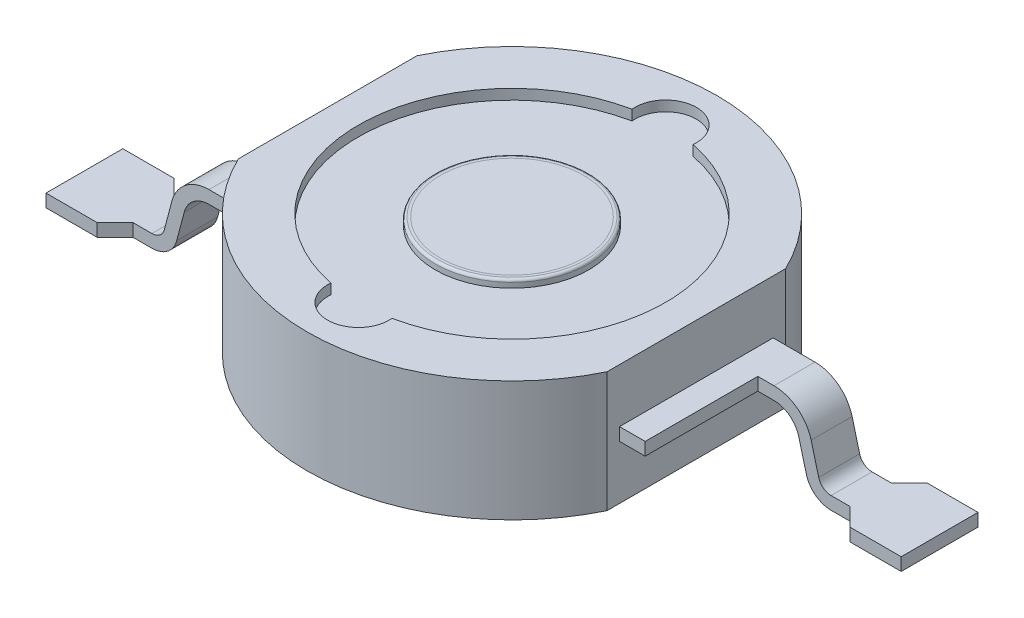
SolidWorks part; units mm, degrees
ref_plane "Front Plane" through (0, 0, 0) normal (0, 0, 1) x (1, 0, 0)
ref_plane "Top Plane" through (0, 0, 0) normal (0, 1, 0) x (1, 0, 0)
ref_plane "Right Plane" through (0, 0, 0) normal (1, 0, 0) x (0, 0, -1)
sketch "Sketch1" plane through (0, 0, 0) normal (0, 1, 0) x (1, 0, 0)
  circle A0 centre (0, 0) radius 4
  dimension "D1" = 8
extrude "Extrude1" add sketch "Sketch1" along normal blind 2.6
sketch "Sketch2" plane through (0, 2.6, 0) normal (0, 1, 0) x (1, 0, 0)
  line L0 (0, 4) -> (0, -4) construction
  line L1 (-3.6, 4) -> (3.6, 4)
  line L2 (-3.6, 4) -> (-3.6, -4)
  line L3 (-3.6, -4) -> (3.6, -4)
  line L4 (3.6, 4) -> (3.6, -4)
  circle A0 centre (0, 0) radius 4 construction
  arc A1 (-0.597, 2.94) -> (-0.597, -2.94) centre (0, 0) ccw
  arc A2 (-0.597, -2.94) -> (0.597, -2.94) centre (0, -3) ccw
  arc A3 (0.597, 2.94) -> (-0.597, 2.94) centre (0, 3) ccw
  arc A4 (0.597, -2.94) -> (0.597, 2.94) centre (0, 0) ccw
  arc A5 (-0.597, 2.94) -> (0.597, 2.94) centre (0, 0) cw construction
  arc A6 (0.597, -2.94) -> (-0.597, -2.94) centre (0, 0) cw construction
  point P4 (0, 4)
  circle M1 centre (0, 0) radius 4
  dimension "D2" = 6
  dimension "D4" = 0.6
  dimension "D1" = 7.2
extrude "Extrude2" cut sketch "Sketch2" against normal up to next (2.6 mm away) flip side to cut contours A2 A4 A3 A1 | L4 L2 A4 A2 A1 A3 M1 region at (2.0672, 2.6, -3.2981) region at (0, 2.6, 0)
extrude "Cut-Extrude1" cut sketch "Sketch2<3>" against normal blind 0.2 contours A2 A4 A3 A1 region at (0, 2.6, 0)
sketch "Sketch2<3>" plane through (0, 2.6, 0) normal (0, 1, 0) x (1, 0, 0) same geometry as "Sketch2"
sketch "Sketch12" plane through (0, 2.4, 0) normal (0, 1, 0) x (1, 0, 0)
  circle A0 centre (0, 0) radius 1.4
  circle A1 centre (0, 0) radius 1.5
  dimension "D1" = 3
  dimension "D2" = 2.8
extrude "Boss-Extrude3" add sketch "Sketch12" along normal blind 0.15 contours A1 A0 | A0 region at (0, 2.4, 0) region at (-1.4576, 2.4, 0)
split line "Split Line1"
sketch "Sketch12<5>" plane through (0, 2.4, 0) normal (0, 1, 0) x (1, 0, 0) same geometry as "Sketch12"
fillet "Fillet4" radius 0.05 1 edges at (0, 2.55, 1.5)
sketch "Sketch6" plane through (0, 0, 0) normal (0, 0, 1) x (1, 0, 0)
  line L0 (-3.6, 1.3) -> (-4.4167, 1.3)
  line L1 (-4.9, 0.9281) -> (-5.0475, 0.3719)
  line L2 (-5.5308, 0) -> (-7.25, 0)
  line L5 (0, 6.1443) -> (0, -1.5717) construction
  line L6 (-3.6, 0) -> (-3.6, 2.6) construction
  line L7 (-3.6, 0) -> (3.6, 0) construction
  arc A0 (-4.4167, 1.3) -> (-4.9, 0.9281) centre (-4.4167, 0.8) ccw
  arc A1 (-5.5308, 0) -> (-5.0475, 0.3719) centre (-5.5308, 0.5) ccw
  dimension "D1" = 0.5
  dimension "D2" = 14.5
  dimension "D3" = 1.3
  dimension "D4" = 1.3
extrude "Extrude-Thin1" add sketch "Sketch6" against normal mid plane 0.8 from offset 1.1 thin thin type one direction wall 0.25
sketch "Sketch7" plane through (0, 0.25, 0) normal (0, 1, 0) x (1, 0, 0)
  line L0 (-5.9, -0.7) -> (-6.25, -0.35)
  line L1 (-5.5308, -0.7) -> (-7.25, -0.7) construction
  line L2 (-6.25, -0.35) -> (-7.25, -0.35)
  line L3 (-7.25, -0.35) -> (-7.25, -1.85)
  line L4 (-7.25, -1.85) -> (-6.25, -1.85)
  line L5 (-6.25, -1.85) -> (-5.9, -1.5)
  line L6 (-5.5308, -1.5) -> (-7.25, -1.5) construction
  line L7 (-5.9, -1.5) -> (-5.9, -0.7)
  dimension "D1" = 1.5
  dimension "D2" = 45
  dimension "D3" = 1
extrude "Extrude3" add sketch "Sketch7" against normal up to surface (0.25 mm away) up to face at (-6.3904, 0, 1.1)
sketch "Sketch10" plane through (0, 0, 0) normal (0, -1, 0) x (1, 0, 0)
  line L6 (3.6, -1.7436) -> (3.6, 1.7436)
  line L7 (3.6, -1.7436) -> (3.6, 1.7436)
  line L8 (-3.6, 1.7436) -> (-3.6, -1.7436)
  line L9 (-3.6, 1.7436) -> (-3.6, -1.7436)
  circle A0 centre (0, 0) radius 3
  arc A6 (-3.6, -1.7436) -> (3.6, -1.7436) centre (0, 0) ccw
  arc A7 (-3.6, -1.7436) -> (3.6, -1.7436) centre (0, 0) ccw
  arc A8 (3.6, 1.7436) -> (-3.6, 1.7436) centre (0, 0) ccw
  arc A9 (3.6, 1.7436) -> (-3.6, 1.7436) centre (0, 0) ccw
  dimension "D3" = 6
  dimension "D2" = 0
extrude "Extrude6" cut sketch "Sketch10" against normal blind 0.25
sketch "Sketch13" plane through (0, 1.55, 0) normal (0, 1, 0) x (1, 0, 0)
  line L0 (-3.6, 1.7436) -> (-3.6, -1.7436) construction
  line L1 (-3.6, -0.7) -> (-4.1, -0.7)
  line L2 (-3.6, -0.7) -> (-3.6, 1.5)
  line L3 (-3.6, 1.5) -> (-4.1, 1.5)
  line L4 (-4.1, -0.7) -> (-4.1, 1.5)
  line L5 (-3.6, -0.7) -> (-4.4167, -0.7) construction
  dimension "D1" = 0.2436
  dimension "D2" = 0.5
extrude "Boss-Extrude4" add sketch "Sketch13" against normal up to surface (0.25 mm away) up to face at (-4.0083, 1.3, 1.1)
pattern_circular "CirPattern1" count 2 over 360 about axis through (0, 2.6, 0) along (0, -1, 0) of "Extrude3", "Extrude-Thin1", "Boss-Extrude4"
